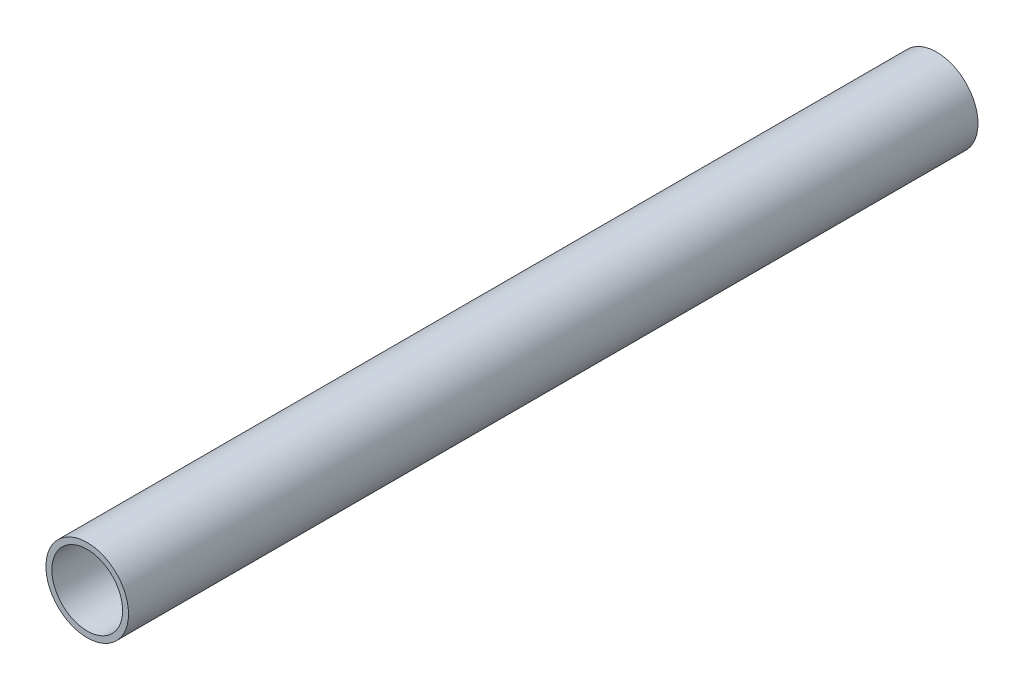
SolidWorks part; units mm, degrees
material "Thornel VCB-20 Carbon Cloth"
ref_plane "Front Plane" through (0, 0, 0) normal (0, 0, 1) x (1, 0, 0)
ref_plane "Top Plane" through (0, 0, 0) normal (0, 1, 0) x (1, 0, 0)
ref_plane "Right Plane" through (0, 0, 0) normal (1, 0, 0) x (0, 0, -1)
sketch "Sketch1" plane through (0, 0, 0) normal (0, 0, 1) x (1, 0, 0)
  circle A0 centre (0, 0) radius 9.525
  circle A1 centre (0, 0) radius 11.1125
  dimension "D1" = 19.05
  dimension "D2" = 22.225
extrude "Boss-Extrude1" add sketch "Sketch1" along normal mid plane 228.6
ref_axis "Axis1" through (0, 0, 157.8671) along (0, 0, -1)
